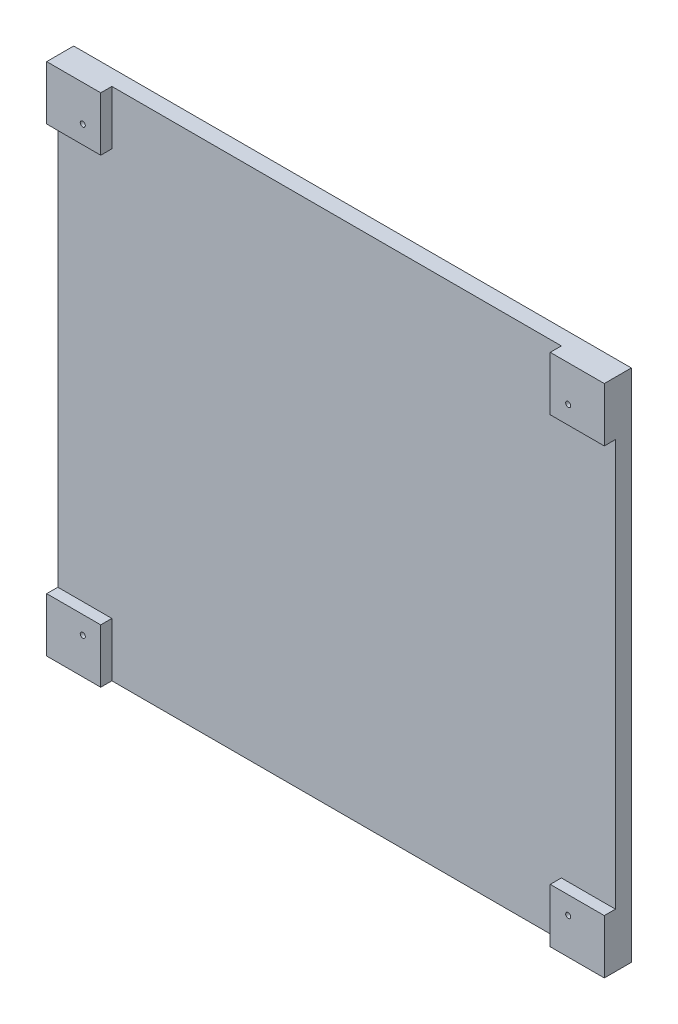
SolidWorks part; units mm, degrees
ref_plane "Front Plane" through (0, 0, 0) normal (1, 0, 0) x (0, 1, 0)
ref_plane "Top Plane" through (0, 0, 0) normal (0, 0, 1) x (0, 1, 0)
ref_plane "Right Plane" through (0, 0, 0) normal (0, 1, 0) x (-1, 0, 0)
sketch "Sketch1" plane through (0, 0, 0) normal (0, 0, 1) x (0, 1, 0)
  line L0 (-75.946, 82.677) -> (-80.946, 82.677) construction
  line L1 (-75.946, 82.677) -> (75.946, 82.677) construction
  line L2 (-75.946, 82.677) -> (-75.946, -82.677) construction
  line L3 (-75.946, -82.677) -> (75.946, -82.677) construction
  line L4 (75.946, 82.677) -> (75.946, -82.677) construction
  line L5 (-75.946, 82.677) -> (75.946, -82.677) construction
  line L6 (-75.946, -82.677) -> (75.946, 82.677) construction
  line L7 (-80.946, 87.677) -> (80.946, 87.677)
  line L8 (-80.946, 87.677) -> (-80.946, -87.677)
  line L9 (-80.946, -87.677) -> (80.946, -87.677)
  line L10 (80.946, 87.677) -> (80.946, -87.677)
  line L11 (-80.946, 87.677) -> (80.946, -87.677) construction
  line L12 (-80.946, -87.677) -> (80.946, 87.677) construction
  line L13 (-75.946, 82.677) -> (-75.946, 87.677) construction
  point P0 (0, 0)
  point P6 (0, 0)
  dimension "D1" = 151.892
  dimension "D2" = 165.354
  dimension "D3" = 5
extrude "Boss-Extrude1" add sketch "Sketch1" along normal blind 5
sketch "Sketch2" plane through (0, 0, 5) normal (0, 0, 1) x (1, 0, 0)
  line L1 (87.677, 80.946) -> (70.677, 80.946)
  line L2 (87.677, 80.946) -> (87.677, 63.946)
  line L3 (87.677, 63.946) -> (70.677, 63.946)
  line L4 (70.677, 80.946) -> (70.677, 63.946)
  line L5 (87.677, -80.946) -> (70.677, -80.946)
  line L6 (87.677, -80.946) -> (87.677, -63.946)
  line L7 (87.677, -63.946) -> (70.677, -63.946)
  line L8 (70.677, -80.946) -> (70.677, -63.946)
  line L9 (-87.677, -80.946) -> (-70.677, -80.946)
  line L10 (-87.677, -80.946) -> (-87.677, -63.946)
  line L11 (-87.677, -63.946) -> (-70.677, -63.946)
  line L12 (-70.677, -80.946) -> (-70.677, -63.946)
  line L13 (-87.677, 80.946) -> (-70.677, 80.946)
  line L14 (-87.677, 80.946) -> (-87.677, 63.946)
  line L15 (-87.677, 63.946) -> (-70.677, 63.946)
  line L16 (-70.677, 80.946) -> (-70.677, 63.946)
  line M3 (87.677, 80.946) -> (-87.677, 80.946)
  line M4 (-87.677, 80.946) -> (-87.677, -80.946)
  line M5 (-87.677, -80.946) -> (87.677, -80.946)
  line M6 (87.677, -80.946) -> (87.677, 80.946)
  dimension "D1" = 17
extrude "Boss-Extrude2" add sketch "Sketch2" along normal blind 3.5 contours L12 L11 M5 M4 | L8 L7 M5 M6 | L4 L3 M3 M6 | L16 L15 M3 M4 region at (79.177, 72.446, 5) region at (-79.177, 72.446, 5) region at (79.177, -72.446, 5) region at (-79.177, -72.446, 5)
sketch "Sketch3" plane through (0, 0, 8.5) normal (0, 0, 1) x (1, 0, 0)
  line L2 (0, 0) -> (0, -50000) construction
  line L3 (0, 0) -> (50000, 0) construction
  circle A0 centre (-76.327, 69.596) radius 0.8
  circle A1 centre (-76.327, -69.596) radius 0.8
  circle A2 centre (76.327, -69.596) radius 0.8
  circle A3 centre (76.327, 69.596) radius 0.8
  dimension "D3" = 1.6
  dimension "D1" = 152.654
  dimension "D2" = 139.192
extrude "Cut-Extrude1" cut sketch "Sketch3" against normal through all contours A0 | A3 | A2 | A1 region at (-76.327, 69.596, 8.5) region at (-76.327, -69.596, 8.5) region at (76.327, -69.596, 8.5) region at (76.327, 69.596, 8.5)
